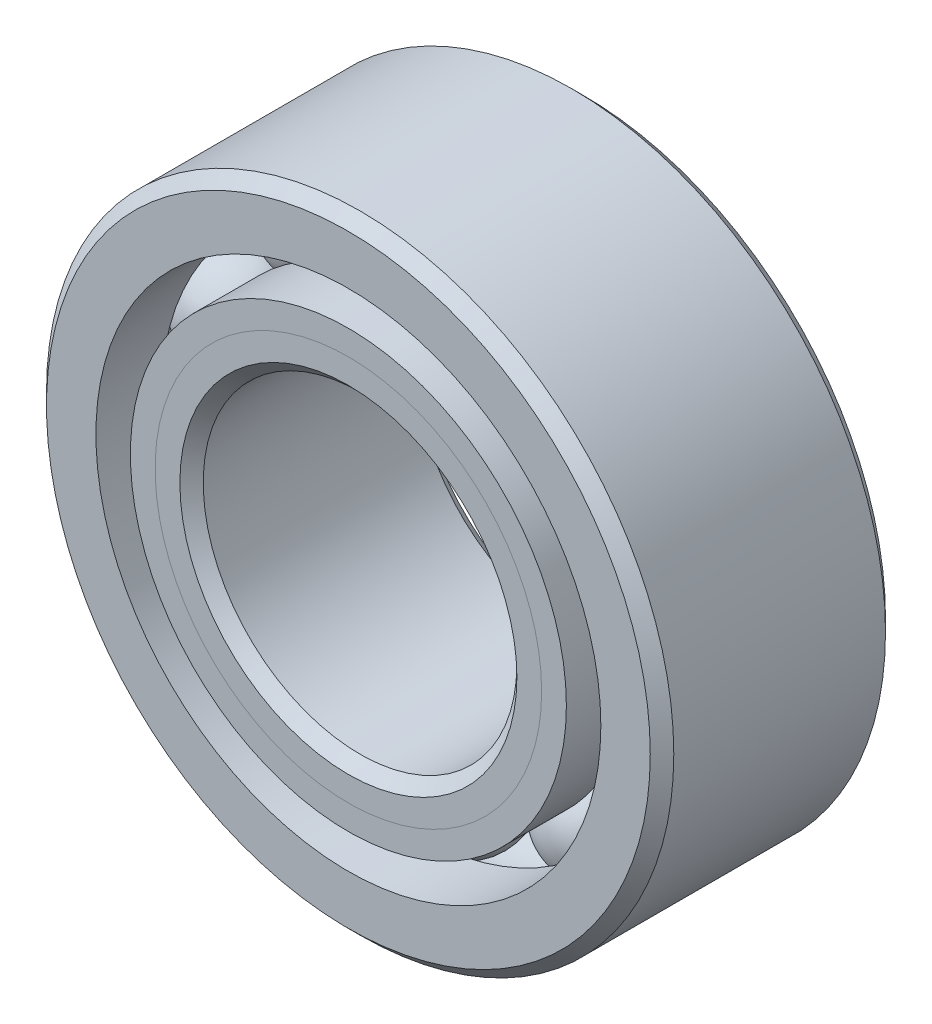
SolidWorks part; units mm, degrees
material "1.4310 (X10CrNi18-8)"
ref_plane "Front Plane" through (0, 0, 0) normal (0, 0, 1) x (1, 0, 0)
ref_plane "Top Plane" through (0, 0, 0) normal (0, 1, 0) x (1, 0, 0)
ref_plane "Right Plane" through (0, 0, 0) normal (1, 0, 0) x (0, 0, -1)
sketch "Sketch1" plane through (0, 0, 0) normal (1, 0, 0) x (0, 0, -1)
  line L0 (-1.1906, 0) -> (1.1906, 0) construction
  line L1 (0, 3.175) -> (0, -3.175) construction
  line L2 (1.0716, 3.175) -> (-1.0716, 3.175)
  line L3 (-1.0716, 3.175) -> (-1.1906, 3.0559)
  line L4 (-1.1906, 3.0559) -> (-1.1906, 2.5557)
  line L5 (-1.1906, 2.5557) -> (-0.5292, 2.5557)
  line L6 (1.1906, 2.5557) -> (0.5292, 2.5557)
  line L7 (1.1906, 3.0559) -> (1.1906, 2.5557)
  line L8 (1.0716, 3.175) -> (1.1906, 3.0559)
  line L9 (0, 3.175) -> (0, 2.3812) construction
  line L10 (0, 2.3812) -> (0, 1.5875) construction
  arc A0 (-0.5292, 2.5557) -> (0.5292, 2.5557) centre (0, 2.3812) cw
  point P14 (0, 1.5875)
  dimension "Width" = 2.3813
  dimension "OD" = 6.35
  dimension "D1" = 45
  dimension "D2" = 0.1191
  dimension "D3" = 1.0583
  dimension "D4" = 0.1745
revolve "Revolve1" add sketch "Sketch1" angle 360 about L0
sketch "Sketch2" plane through (0, 0, 0) normal (1, 0, 0) x (0, 0, -1)
  line L0 (-1.1906, 2.2068) -> (-0.5292, 2.2068)
  line L1 (-1.1906, 3.0559) -> (-1.1906, -3.0559) construction
  line L2 (-1.1906, 2.2068) -> (-1.1906, 1.9563)
  line L3 (-1.1906, 1.9563) -> (-0.9401, 1.7058)
  line L4 (-0.9401, 1.7058) -> (0, 1.7058)
  line L5 (0, 3.175) -> (0, -3.175) construction
  line L6 (0, 1.7058) -> (0, 1.8241)
  line L7 (0, 1.8241) -> (0, 1.5875) construction
  line L8 (-1.1906, 2.2068) -> (-1.1906, 1.7058) construction
  line L9 (-1.1906, 1.7058) -> (-0.9401, 1.7058) construction
  arc A0 (-0.5292, 2.2068) -> (0, 1.8241) centre (0, 2.3812) ccw
  arc A1 (0.5292, 2.5557) -> (-0.5292, 2.5557) centre (0, 2.3812) ccw construction
  circle A2 centre (0, 2.3812) radius 0.5572 construction
  dimension "D1" = 45
revolve "Revolve2" add sketch "Sketch2" angle 360 about L0
sketch "Sketch3" plane through (0, 0, 0) normal (1, 0, 0) x (0, 0, -1)
  line L0 (-1.1906, 1.9563) -> (-0.9401, 1.7058)
  line L1 (-0.9401, 1.7058) -> (0, 1.7058)
  line L2 (0, 1.7058) -> (0, 1.8241)
  line L3 (-1.1906, 1.9563) -> (-1.1906, 1.7058)
  line L4 (-1.1906, 2.2068) -> (-1.1906, 1.7058) construction
  line L5 (-1.1906, 1.7058) -> (-1.0723, 1.5875)
  line L6 (-1.0723, 1.5875) -> (1.0716, 1.5875)
  line L7 (1.0716, 3.175) -> (1.0716, -3.175) construction
  line L8 (1.0716, 1.5875) -> (1.1906, 1.7066)
  line L9 (1.1906, -3.0559) -> (1.1906, 3.0559) construction
  line L10 (1.1906, 1.7066) -> (1.1906, 2.2068)
  line L11 (1.1906, 2.2068) -> (0.5292, 2.2068)
  line L13 (1.0716, 3.175) -> (1.1906, 3.0559) construction
  circle A0 centre (0, 2.3812) radius 0.5572 construction
  arc A1 (0.5292, 2.2068) -> (0, 1.8241) centre (0, 2.3812) cw
revolve "Revolve3" add sketch "Sketch3" angle 360 about L0
sketch "Sketch4" plane through (0, 0, 0) normal (1, 0, 0) x (0, 0, -1)
  line L0 (-0.5572, 2.3812) -> (0.5572, 2.3812)
  circle A1 centre (0, 2.3812) radius 0.5572 construction
  arc A2 (-0.5572, 2.3812) -> (0.5572, 2.3812) centre (0, 2.3812) cw
  arc A3 (0.5292, 2.5557) -> (-0.5292, 2.5557) centre (0, 2.3812) ccw construction
revolve "Revolve4" add sketch "Sketch4" angle 360 about L0
ref_axis "Axis1" through (0, 0, -1.1906) along (0, 0, 1)
pattern_circular "CirPattern1" count 10 every 36 about axis through (0, 0, -1.1906) along (0, 0, 1) of bodies 104
equation "\"D2@Sketch1\" = \"Width@Sketch1\"*.05"
equation "\"D3@Sketch1\" = \"Width@Sketch1\"/2.25"
equation "\"D4@Sketch1\" = (((\"OD@Sketch1\"-\"Width@Sketch1\")/2)/3.25)/3.5"
equation "\"D2@CirPattern1\" = 360/\"Balls@CirPattern1\""
